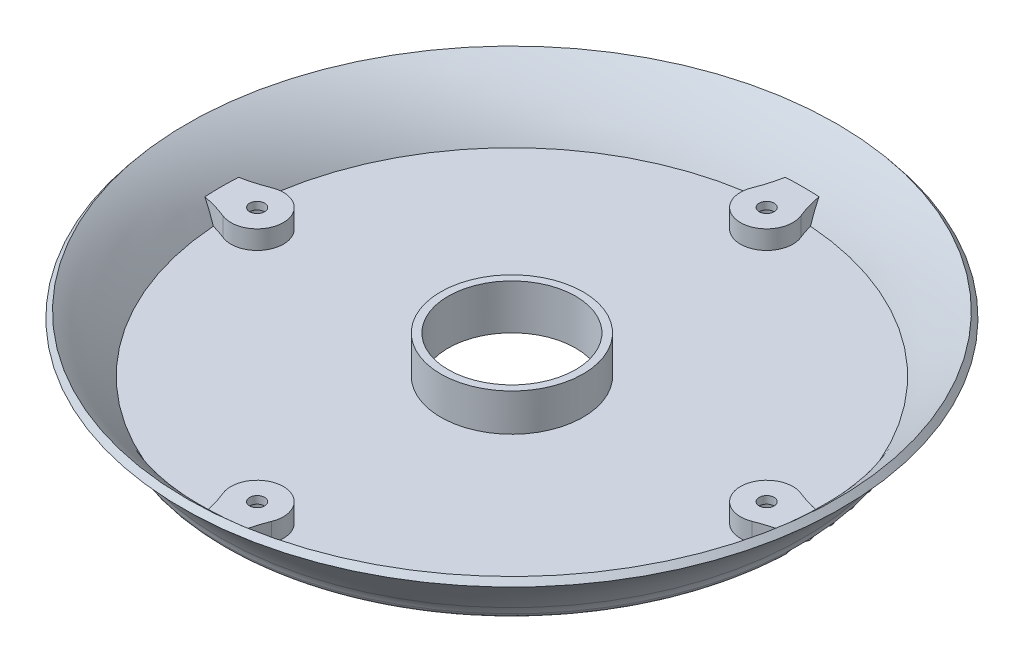
SolidWorks part; units mm, degrees
ref_plane "Front Plane" through (0, 0, 0) normal (0, 0, 1) x (1, 0, 0)
ref_plane "Top Plane" through (0, 0, 0) normal (0, 1, 0) x (1, 0, 0)
ref_plane "Right Plane" through (0, 0, 0) normal (1, 0, 0) x (0, 0, -1)
sketch "Sketch1" plane through (0, 0, 0) normal (0, 0, 1) x (1, 0, 0)
  line L0 (-25.5, 30) -> (-25.5, 0) construction
  line L1 (-25.5, 0) -> (-70, 0) construction
  line L2 (0, 0) -> (0, 35) construction
  line L3 (-70, 0) -> (-86.7157, 35) construction
  arc A0 (-70, 0) -> (-86.7157, 35) centre (-115, 0) ccw
  dimension "D1" = 35
  dimension "D5" = 45
  dimension "D2" = 30
  dimension "D3" = 70
  dimension "D4" = 25.5
  dimension "D7" = 35
revolve "Revolve-Thin1" add sketch "Sketch1" angle 360 about L2 wall 2
ref_plane "Plane1" through (0, 25, 0) normal (0, -1, 0) x (-1, 0, 0)
sketch "Sketch2" plane through (0, 25, 0) normal (0, -1, 0) x (-1, 0, 0)
  line L0 (-68, 0) -> (-86.7157, 0) construction
  line L1 (-86.7157, -4) -> (-86.7157, 4)
  line L2 (-4, 86.7157) -> (4, 86.7157)
  line L3 (0, 68) -> (0, 86.7157) construction
  line L4 (86.7157, 4) -> (86.7157, -4)
  line L5 (68, 0) -> (81.3633, 0) construction
  line L6 (4, -86.7157) -> (-4, -86.7157)
  line L7 (0, -68) -> (0, -86.7157) construction
  circle A0 centre (-68, 0) radius 2
  arc A1 (-70.6098, -6.4953) -> (-70.6098, 6.4953) centre (-68, 0) ccw
  circle A2 centre (0, 0) radius 86.7157 construction
  arc A3 (-86.6237, 3.9932) -> (-86.6237, -3.9932) centre (0, 0) ccw
  arc A4 (-70.6098, 6.4953) -> (-86.7157, 4) centre (-84.0314, 39.8998) cw
  arc A5 (-70.6098, -6.4953) -> (-86.7157, -4) centre (-84.0314, -39.8998) ccw
  arc A6 (6.4953, 70.6098) -> (4, 86.7157) centre (39.8998, 84.0314) cw
  arc A7 (-6.4953, 70.6098) -> (6.4953, 70.6098) centre (0, 68) ccw
  circle A8 centre (0, 68) radius 2
  arc A9 (-6.4953, 70.6098) -> (-4, 86.7157) centre (-39.8998, 84.0314) ccw
  arc A10 (70.6098, -6.4953) -> (86.7157, -4) centre (84.0314, -39.8998) cw
  arc A11 (70.6098, 6.4953) -> (70.6098, -6.4953) centre (68, 0) ccw
  circle A12 centre (68, 0) radius 2
  arc A13 (70.6098, 6.4953) -> (86.7157, 4) centre (84.0314, 39.8998) ccw
  arc A14 (-6.4953, -70.6098) -> (-4, -86.7157) centre (-39.8998, -84.0314) cw
  arc A15 (6.4953, -70.6098) -> (-6.4953, -70.6098) centre (0, -68) ccw
  circle A16 centre (0, -68) radius 2
  arc A17 (6.4953, -70.6098) -> (4, -86.7157) centre (39.8998, -84.0314) ccw
  point P5 (0, 0)
  point P10 (-86.7157, 0)
  point P15 (0, 0)
  point P16 (0, 0)
  point P44 (0, 0)
  point P45 (0, 0)
  point P46 (0, 0)
  point P47 (0, 0)
  point P48 (0, 0)
  point P49 (0, 0)
  dimension "D1" = 4
  dimension "D2" = 14
  dimension "D4" = 36
  dimension "D5" = 68
  dimension "D3" = 8
  dimension "D6" = 68
  dimension "D7" = 68
  dimension "D8" = 68
extrude "Boss-Extrude1" add sketch "Sketch2" along normal up to surface (25 mm away) contours A17 A15 A14 L6 A16 | A13 A11 A10 L4 A12 | A9 A7 A6 L2 A8 | A5 A1 A4 A3 A0 region at (73.1963, 25, 0) region at (0, 25, -73.2096) region at (-73.2096, 25, 0) region at (0, 25, 73.2096) up to face at (0, 0, -72)
sketch "Sketch3" plane through (0, 0, 0) normal (0, 0, 1) x (1, 0, 0)
  line L0 (-72, 0) -> (-99.1272, 0)
  line L1 (-99.1272, 0) -> (-99.1272, 33.4444)
  line L3 (-99.1272, 33.4444) -> (-87.9728, 33.4444)
  arc A0 (-70, 0) -> (-86.7157, 35) centre (-115, 0) ccw construction
  arc A4 (-72, 0) -> (-87.9728, 33.4444) centre (-115, 0) ccw
  arc A5 (-72, 0) -> (-87.9728, 33.4444) centre (-115, 0) ccw
  dimension "D1" = 2
revolve "Cut-Revolve1" cut sketch "Sketch3" angle 360 about L2
sketch "Sketch4" plane through (0, 0, 0) normal (1, 0, 0) x (0, 0, -1)
  line L0 (86.7157, 35) -> (-86.7157, 35) construction
  line L1 (-90, 0) -> (90, 0)
  line L2 (-90, 0) -> (-90, 20)
  line L3 (-90, 20) -> (90, 20)
  line L4 (90, 0) -> (90, 20)
  line L5 (-72, 0) -> (72, 0) construction
  point P8 (0, 0)
  dimension "D1" = 15
  dimension "D2" = 180
extrude "Cut-Extrude1" cut sketch "Sketch4" against normal up to surface and the other way up to surface up to face at (0, 0, -72) other way up to face at (0, 0, -72)
sketch "Sketch5" plane through (0, 20, 0) normal (0, -1, 0) x (1, 0, 0)
  circle A0 centre (0, 0) radius 76.9343 construction
  circle A1 centre (0, 0) radius 76.9343
  circle A2 centre (68, 0) radius 2 construction
  circle A3 centre (68, 0) radius 2
  circle A4 centre (0, 68) radius 2 construction
  circle A5 centre (-68, 0) radius 2 construction
  circle A6 centre (0, -68) radius 2 construction
  circle A7 centre (0, 68) radius 2
  circle A8 centre (-68, 0) radius 2
  circle A9 centre (0, -68) radius 2
extrude "Boss-Extrude2" add sketch "Sketch5" along normal blind 2
sketch "Sketch6" plane through (0, 18, 0) normal (0, -1, 0) x (1, 0, 0)
  circle A2 centre (0, 68) radius 5
  circle A3 centre (0, 68) radius 5
  circle A5 centre (68, 0) radius 5
  circle A6 centre (68, 0) radius 5
  circle A8 centre (0, -68) radius 5
  circle A9 centre (0, -68) radius 5
  circle A11 centre (-68, 0) radius 5
  circle A12 centre (-68, 0) radius 5
  dimension "D1" = 3
  dimension "D2" = 3
  dimension "D3" = 3
  dimension "D4" = 3
extrude "Cut-Extrude2" cut sketch "Sketch6" against normal blind 5
fillet "Fillet1" radius 2 1 edges at (0, 18, -76.9343)
fillet "Fillet2" radius 10 1 edges at (0, 20, -76.9343)
sketch "Sketch8" plane through (0, 18, 0) normal (0, -1, 0) x (1, 0, 0)
  circle A0 centre (0, 0) radius 17
  dimension "D1" = 34
extrude "Cut-Extrude3" cut sketch "Sketch8" against normal up to next
sketch "Sketch9" plane through (0, 20, 0) normal (0, 1, 0) x (1, 0, 0)
  circle A0 centre (0, 0) radius 17 construction
  circle A1 centre (0, 0) radius 17
  circle A2 centre (0, 0) radius 19
  dimension "D1" = 2
extrude "Boss-Extrude3" add sketch "Sketch9" along normal blind 10
